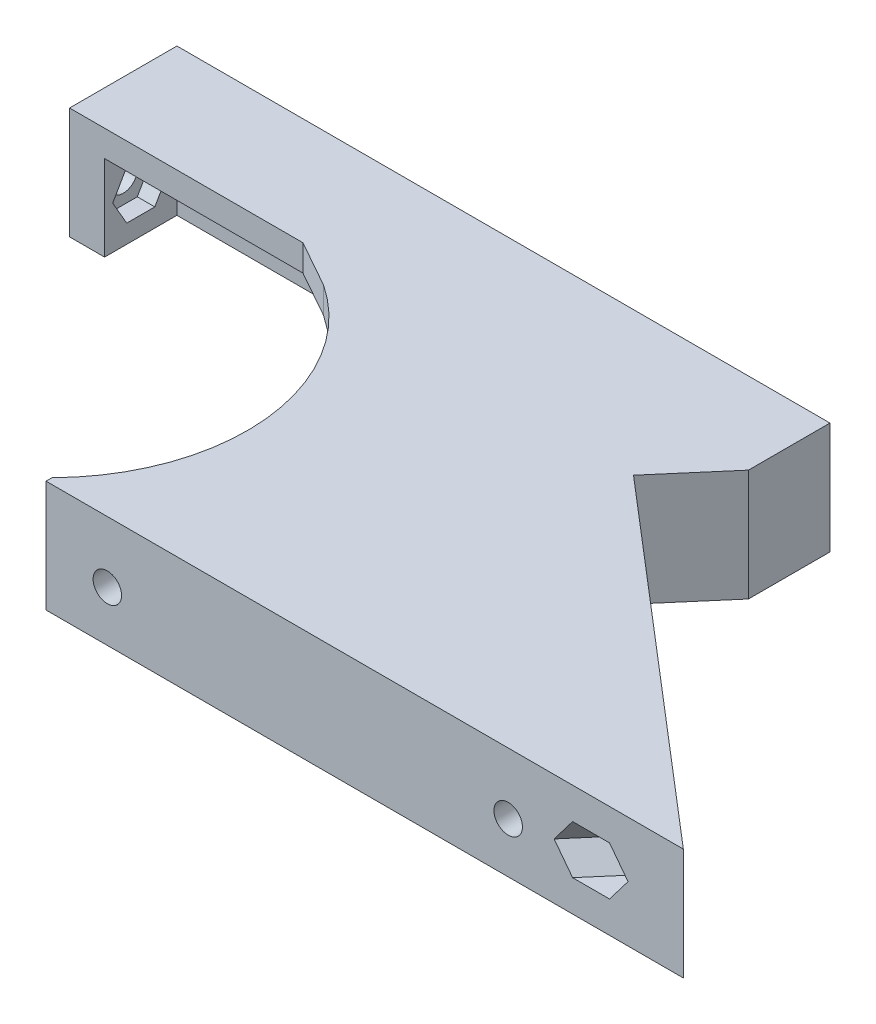
SolidWorks part; units mm, degrees
ref_plane "Alzado" through (0, 0, 0) normal (0, 0, 1) x (1, 0, 0)
ref_plane "Planta" through (0, 0, 0) normal (0, 1, 0) x (1, 0, 0)
ref_plane "Vista lateral" through (0, 0, 0) normal (1, 0, 0) x (0, 0, -1)
sketch "Croquis1" plane through (0, 0, 0) normal (0, 1, 0) x (1, 0, 0)
  line L0 (0, 0) -> (72.7832, 0)
  line L1 (72.7832, 0) -> (38.2245, 29.6204)
  line L2 (38.2245, 29.6204) -> (35.6214, 26.5833)
  line L3 (35.6214, 26.5833) -> (60.8031, 5)
  line L4 (60.8031, 5) -> (0, 5)
  line L5 (0, 5) -> (0, 0)
  dimension "D1" = 4
  dimension "D2" = 5
  dimension "D3" = 40.6
  dimension "D4" = 72.7832
extrude "Saliente-Extruir1" add sketch "Croquis1" along normal blind 12.75
sketch "Croquis2" plane through (0, 0, 0) normal (0, 0, 1) x (1, 0, 0)
  line L2 (0, 12.75) -> (72.7832, 12.75) construction
  line L3 (72.7832, 12.75) -> (72.7832, 0) construction
  circle A0 centre (52.7832, 5.75) radius 1.625
  circle A1 centre (7, 5.75) radius 1.625
  dimension "D1" = 3.25
  dimension "D2" = 20
  dimension "D3" = 7
  dimension "D4" = 45.7832
  dimension "D5" = 7
extrude "Cortar-Extruir1" cut sketch "Croquis2" against normal up to next
sketch "Croquis3" plane through (0, 12.75, 0) normal (0, 1, 0) x (1, 0, 0)
  line L0 (0, 5) -> (0, 0) construction
  line L1 (0, 0) -> (72.7832, 0) construction
  circle A0 centre (-16, 16.5) radius 22.5
  dimension "D1" = 45
  dimension "D2" = 16
  dimension "D3" = 16.5
extrude "Cortar-Extruir2" cut sketch "Croquis3" against normal through all
sketch "Croquis4" plane through (0, 12.75, 0) normal (0, 1, 0) x (1, 0, 0)
  line L0 (38.2245, 29.6204) -> (31.6563, 35.25)
  line L1 (31.6563, 35.25) -> (-3.5627, 35.25)
  line L2 (0, 0) -> (72.7832, 0) construction
  line L3 (72.7832, 0) -> (38.2245, 29.6204) construction
  line L4 (38.2245, 29.6204) -> (35.6214, 26.5833)
  line L5 (35.6214, 26.5833) -> (60.8031, 5)
  line L6 (60.8031, 5) -> (3.3391, 5)
  arc A0 (3.3391, 5) -> (-3.5627, 35.25) centre (-16, 16.5) ccw
  arc A1 (0, 0.6807) -> (3.3391, 5) centre (-16, 16.5) ccw construction
  dimension "D1" = 35.25
extrude "Saliente-Extruir2" add sketch "Croquis4" against normal blind 3
sketch "Croquis5" plane through (0, 9.75, 0) normal (0, -1, 0) x (1, 0, 0)
  line L0 (-3.5627, -35.25) -> (31.6563, -35.25)
  line L1 (31.6563, -35.25) -> (38.2245, -29.6204)
  line L2 (38.2245, -29.6204) -> (35.6214, -26.5833)
  line L3 (35.6214, -26.5833) -> (30.1767, -31.25)
  line L4 (30.1767, -31.25) -> (0.9908, -31.25)
  arc A0 (-3.5627, -35.25) -> (3.3391, -5) centre (-16, -16.5) ccw construction
  arc A1 (-3.5627, -35.25) -> (0.9908, -31.25) centre (-16, -16.5) ccw
  dimension "D1" = 4
extrude "Saliente-Extruir3" add sketch "Croquis5" along normal up to vertex (9.75 mm away) up to point (38.2245, 0, -29.6204)
sketch "Croquis6" plane through (30.8242, 0, -35.9632) normal (0.6508, 0, -0.7593) x (-0.7593, 0, -0.6508)
  line L0 (-55.2622, 12.75) -> (-55.2622, 0) construction
  circle A0 centre (-47.2622, 6.375) radius 1.625
  circle A1 centre (-7.4422, 6.375) radius 1.625
  dimension "D1" = 3.25
  dimension "D2" = 3.25
  dimension "D3" = 8
  dimension "D5" = 39.82
extrude "Cortar-Extruir3" cut sketch "Croquis6" against normal blind 10
sketch "Croquis7" plane through (28.2211, 0, -32.9261) normal (-0.6508, 0, 0.7593) x (0.7593, 0, 0.6508)
  line L1 (48.8643, 3.6) -> (50.4665, 6.375)
  line L2 (50.4665, 6.375) -> (48.8643, 9.15)
  line L3 (48.8643, 9.15) -> (45.66, 9.15)
  line L4 (45.66, 9.15) -> (44.0579, 6.375)
  line L5 (44.0579, 6.375) -> (45.66, 3.6)
  line L6 (45.66, 3.6) -> (48.8643, 3.6)
  circle A0 centre (47.2622, 6.375) radius 2.775 construction
  dimension "D1" = 5.55
extrude "Cortar-Extruir4" cut sketch "Croquis7" along normal blind 10 from offset 2 offset against normal yes
sketch "Croquis8" plane through (28.2211, 0, -32.9261) normal (-0.6508, 0, 0.7593) x (0.7593, 0, 0.6508)
  line L0 (45.66, 3.6) -> (48.8643, 3.6) construction
  line L1 (9.0443, 3.6) -> (10.6465, 6.375)
  line L2 (10.6465, 6.375) -> (9.0443, 9.15)
  line L3 (9.0443, 9.15) -> (5.84, 9.15)
  line L4 (5.84, 9.15) -> (4.2379, 6.375)
  line L5 (4.2379, 6.375) -> (5.84, 3.6)
  line L6 (5.84, 3.6) -> (9.0443, 3.6)
  circle A0 centre (7.4422, 6.375) radius 2.775 construction
extrude "Cortar-Extruir5" cut sketch "Croquis8" along normal blind 10 from offset 2 offset against normal yes
sketch "Croquis9" plane through (0, 0, -5) normal (0, 0, -1) x (-1, 0, 0)
  line L1 (-5.3979, 2.975) -> (-3.7957, 5.75)
  line L2 (-3.7957, 5.75) -> (-5.3979, 8.525)
  line L3 (-5.3979, 8.525) -> (-8.6021, 8.525)
  line L4 (-8.6021, 8.525) -> (-10.2043, 5.75)
  line L5 (-10.2043, 5.75) -> (-8.6021, 2.975)
  line L6 (-8.6021, 2.975) -> (-5.3979, 2.975)
  line L7 (-51.1811, 2.975) -> (-49.5789, 5.75)
  line L8 (-49.5789, 5.75) -> (-51.1811, 8.525)
  line L9 (-51.1811, 8.525) -> (-54.3853, 8.525)
  line L10 (-54.3853, 8.525) -> (-55.9875, 5.75)
  line L11 (-55.9875, 5.75) -> (-54.3853, 2.975)
  line L12 (-54.3853, 2.975) -> (-51.1811, 2.975)
  circle A0 centre (-7, 5.75) radius 2.775 construction
  circle A1 centre (-52.7832, 5.75) radius 2.775 construction
  dimension "D1" = 5.55
extrude "Cortar-Extruir6" cut sketch "Croquis9" against normal blind 2
sketch "Croquis10" plane through (0, 0, -35.25) normal (0, 0, -1) x (-1, 0, 0)
  line L0 (-31.6563, 0) -> (-31.6563, 12.75) construction
  circle A0 centre (-21.6563, 6.375) radius 1.625
  dimension "D1" = 3.25
  dimension "D2" = 10
extrude "Cortar-Extruir7" cut sketch "Croquis10" against normal up to next
sketch "Croquis11" plane through (0, 0, -31.25) normal (0, 0, 1) x (1, 0, 0)
  line L1 (23.2585, 3.6) -> (24.8606, 6.375)
  line L2 (24.8606, 6.375) -> (23.2585, 9.15)
  line L3 (23.2585, 9.15) -> (20.0542, 9.15)
  line L4 (20.0542, 9.15) -> (18.452, 6.375)
  line L5 (18.452, 6.375) -> (20.0542, 3.6)
  line L6 (20.0542, 3.6) -> (23.2585, 3.6)
  circle A0 centre (21.6563, 6.375) radius 2.775 construction
  dimension "D1" = 5.55
extrude "Cortar-Extruir8" cut sketch "Croquis11" against normal blind 2
mirror "Simetría1" about plane through (0, 0, 0) normal (0, 1, 0) of bodies 111
sketch "Croquis12" plane through (0, 0, -35.25) normal (0, 0, -1) x (-1, 0, 0)
  line L1 (-79.3319, 0) -> (13.1768, 0)
  line L2 (-79.3319, 0) -> (-79.3319, 24.2558)
  line L3 (-79.3319, 24.2558) -> (13.1768, 24.2558)
  line L4 (13.1768, 0) -> (13.1768, 24.2558)
extrude "Cortar-Extruir9" cut sketch "Croquis12" against normal through all both and the other way through all
sketch "Croquis13" plane through (0, -12.75, 0) normal (0, -1, 0) x (1, 0, 0)
  line L1 (-35.5627, -82.3826) -> (-35.5627, -38.25)
  line L3 (-3.5627, -35.25) -> (31.6563, -35.25)
  line L5 (31.6563, -35.25) -> (0.0002, -62.3826)
  line L6 (0.0002, -62.3826) -> (-35.5627, -82.3826)
  line L7 (72.7832, 0) -> (31.6563, -35.25) construction
  line L8 (-3.5627, -35.25) -> (-8.9133, -38.25)
  line L9 (-8.9133, -38.25) -> (-35.5627, -38.25)
  dimension "D1" = 32
  dimension "D2" = 3
  dimension "D3" = 20
extrude "Saliente-Extruir4" add sketch "Croquis13" against normal up to vertex (12.75 mm away) up to point (31.6563, 0, -35.25)
sketch "Croquis14" plane through (0, 0, 0) normal (0, 1, 0) x (1, 0, 0)
  line L3 (30.1767, 31.25) -> (0.9908, 31.25)
  line L4 (0.9908, 31.25) -> (-31.5627, 38.25)
  line L6 (-31.5627, 38.25) -> (-31.5627, 75.5439)
  line L7 (-2.3039, 59.0892) -> (70.1801, -3.0371)
  line L8 (-31.5627, 75.5439) -> (-2.3039, 59.0892)
  line L9 (-31.5627, 38.25) -> (-31.5627, 75.5439)
  line L10 (-2.3039, 59.0892) -> (30.1767, 31.25)
  line L11 (-31.5627, 75.5439) -> (-2.3039, 59.0892)
  dimension "D1" = 4
extrude "Cortar-Extruir10" cut sketch "Croquis14" against normal up to vertex (9.75 mm away) up to point (0.9908, -9.75, -31.25)
sketch "Croquis16" plane through (30.8242, 0, -35.9632) normal (0.6508, 0, -0.7593) x (-0.7593, 0, -0.6508)
  line L0 (40.5969, 0) -> (-55.2622, 0) construction
  line L1 (-27.4422, 0) -> (40.5969, 0)
  line L2 (-27.4422, 0) -> (-27.4422, -12.75)
  line L3 (-27.4422, -12.75) -> (40.5969, -12.75)
  line L4 (40.5969, 0) -> (40.5969, -12.75)
  circle A0 centre (-7.4422, -6.375) radius 1.625 construction
  dimension "D1" = 20
  dimension "D2" = 68.0391
extrude "Cortar-Extruir11" cut sketch "Croquis16" against normal blind 1
sketch "Croquis17" plane through (0, -12.75, 0) normal (0, -1, 0) x (1, 0, 0)
  line L1 (0.0002, -61.6233) -> (-40.6573, -61.6233)
  line L2 (0.0002, -61.6233) -> (0.0002, -84.5579)
  line L3 (0.0002, -84.5579) -> (-40.6573, -84.5579)
  line L4 (-40.6573, -61.6233) -> (-40.6573, -84.5579)
extrude "Cortar-Extruir12" cut sketch "Croquis17" against normal through all both and the other way through all
sketch "Croquis18" plane through (0, 0, 0) normal (0, 1, 0) x (1, 0, 0)
  line L0 (60.8031, 5) -> (-2.3039, 59.0892) construction
  line L1 (-35.5627, 61.6233) -> (-0.6506, 61.6233)
  line L2 (-35.5627, 61.6233) -> (-35.5627, 57.6722)
  line L3 (-35.5627, 57.6722) -> (-0.6506, 57.6722)
  line L4 (-0.6506, 61.6233) -> (-0.6506, 57.6722)
extrude "Saliente-Extruir5" add sketch "Croquis18" against normal up to surface (9.75 mm away) up to face at (-1.8156, -9.75, -38.1832)
sketch "Croquis20" plane through (30.1734, 0, -35.2039) normal (0.6508, 0, -0.7593) x (-0.7593, 0, -0.6508)
  line L2 (40.5969, -12.75) -> (40.5969, 0) construction
  circle A0 centre (25.5969, -6.375) radius 1.625
  circle A1 centre (-7.4422, -6.375) radius 1.625 construction
  circle A2 centre (-7.4422, -6.375) radius 1.625
  dimension "D2" = 33.0391
  dimension "D1" = 15
extrude "Cortar-Extruir14" cut sketch "Croquis20" against normal blind 10
sketch "Croquis21" plane through (28.2211, 0, -32.9261) normal (-0.6508, 0, 0.7593) x (0.7593, 0, 0.6508)
  line L0 (9.0443, -9.15) -> (5.84, -9.15) construction
  line L1 (-23.9947, -9.15) -> (-22.3926, -6.375)
  line L2 (-22.3926, -6.375) -> (-23.9947, -3.6)
  line L3 (-23.9947, -3.6) -> (-27.199, -3.6)
  line L4 (-27.199, -3.6) -> (-28.8012, -6.375)
  line L5 (-28.8012, -6.375) -> (-27.199, -9.15)
  line L6 (-27.199, -9.15) -> (-23.9947, -9.15)
  circle A0 centre (-25.5969, -6.375) radius 2.775 construction
extrude "Cortar-Extruir15" cut sketch "Croquis21" against normal up to vertex (2 mm away) up to point (36.3898, -9.15, -28.5588)
sketch "Croquis22" plane through (0, 0, -61.6233) normal (0, 0, -1) x (-1, 0, 0)
  line L0 (35.5627, -12.75) -> (35.5627, 0) construction
  circle A0 centre (18.1127, -6.375) radius 1.625
  dimension "D1" = 3.25
  dimension "D2" = 17.45
extrude "Cortar-Extruir16" cut sketch "Croquis22" against normal blind 10
sketch "Croquis23" plane through (0, 0, -57.6722) normal (0, 0, 1) x (1, 0, 0)
  line L0 (7.5697, -9.15) -> (10.0026, -9.15) construction
  line L1 (-16.5105, -9.15) -> (-14.9084, -6.375)
  line L2 (-14.9084, -6.375) -> (-16.5105, -3.6)
  line L3 (-16.5105, -3.6) -> (-19.7148, -3.6)
  line L4 (-19.7148, -3.6) -> (-21.317, -6.375)
  line L5 (-21.317, -6.375) -> (-19.7148, -9.15)
  line L6 (-19.7148, -9.15) -> (-16.5105, -9.15)
  circle A0 centre (-18.1127, -6.375) radius 2.775 construction
extrude "Cortar-Extruir17" cut sketch "Croquis23" against normal blind 2
sketch "Croquis26" plane through (0, 0, 0) normal (0, 1, 0) x (1, 0, 0)
  line L0 (60.8031, 5) -> (-2.2878, 59.0754)
  line L1 (60.8031, 5) -> (60.1523, 4.2407)
  line L2 (-2.2878, 59.0754) -> (-2.9386, 58.3161)
  line L3 (60.1523, 4.2407) -> (-2.9386, 58.3161)
  line L5 (60.8031, 5) -> (-0.6506, 57.6722) construction
  dimension "D1" = 1
extrude "Saliente-Extruir6" add sketch "Croquis26" against normal up to vertex (12.75 mm away) up to point (-0.6506, -12.75, -61.6233)
sketch "Croquis27" plane through (27.5703, 0, -32.1669) normal (-0.6508, 0, 0.7593) x (0.7593, 0, 0.6508)
  line L0 (9.0443, -9.15) -> (5.84, -9.15) construction
  line L1 (-22.4214, -6.375) -> (-24.0092, -3.625)
  line L2 (-24.0092, -3.625) -> (-27.1846, -3.625)
  line L3 (-27.1846, -3.625) -> (-28.7723, -6.375)
  line L4 (-28.7723, -6.375) -> (-27.1846, -9.125)
  line L5 (-27.1846, -9.125) -> (-24.0092, -9.125)
  line L6 (-24.0092, -9.125) -> (-22.4214, -6.375)
  line L7 (10.6465, -6.375) -> (9.0443, -3.6)
  line L8 (9.0443, -3.6) -> (5.84, -3.6)
  line L9 (5.84, -3.6) -> (4.2379, -6.375)
  line L10 (4.2379, -6.375) -> (5.84, -9.15)
  line L11 (5.84, -9.15) -> (9.0443, -9.15)
  line L12 (9.0443, -9.15) -> (10.6465, -6.375)
  circle A0 centre (-25.5969, -6.375) radius 2.75 construction
  circle A1 centre (7.4422, -6.375) radius 2.775 construction
extrude "Cortar-Extruir18" cut sketch "Croquis27" against normal blind 2
sketch "Croquis28" plane through (29.5227, 0, -34.4447) normal (-0.6508, 0, 0.7593) x (0.7593, 0, 0.6508)
  line L1 (-24.0092, -3.625) -> (-27.1846, -3.625)
  line L2 (-27.1846, -3.625) -> (-28.7723, -6.375)
  line L3 (-28.7723, -6.375) -> (-27.1846, -9.125)
  line L4 (-27.1846, -9.125) -> (-24.0092, -9.125)
  line L5 (-24.0092, -9.125) -> (-22.4214, -6.375)
  line L6 (-22.4214, -6.375) -> (-24.0092, -3.625)
  line L7 (10.6465, -6.375) -> (9.0443, -3.6)
  line L8 (9.0443, -3.6) -> (5.84, -3.6)
  line L9 (5.84, -3.6) -> (4.2379, -6.375)
  line L10 (4.2379, -6.375) -> (5.84, -9.15)
  line L11 (5.84, -9.15) -> (9.0443, -9.15)
  line L12 (9.0443, -9.15) -> (10.6465, -6.375)
  circle A0 centre (-25.5969, -6.375) radius 2.75 construction
  circle A1 centre (7.4422, -6.375) radius 2.775 construction
  circle A2 centre (-25.5969, -6.375) radius 1.625
  circle A3 centre (7.4422, -6.375) radius 1.625
extrude "Saliente-Extruir7" add sketch "Croquis28" along normal blind 1
sketch "Croquis29" plane through (-35.5627, 0, 0) normal (-1, 0, 0) x (0, 0, 1)
  line L0 (-61.6233, -12.75) -> (-61.6233, 0) construction
  line L1 (-38.25, 0) -> (-61.6233, 0) construction
  circle A0 centre (-51.6233, -6.375) radius 1.625
  dimension "D3" = 3.25
  dimension "D1" = 10
  dimension "D2" = 6.375
extrude "Cortar-Extruir19" cut sketch "Croquis29" against normal up to next
sketch "Croquis30" plane through (-31.5627, 0, 0) normal (1, 0, 0) x (0, 0, -1)
  line L8 (53.2255, -9.15) -> (54.8276, -6.375)
  line L9 (54.8276, -6.375) -> (53.2255, -3.6)
  line L10 (53.2255, -3.6) -> (50.0212, -3.6)
  line L11 (50.0212, -3.6) -> (48.419, -6.375)
  line L12 (48.419, -6.375) -> (50.0212, -9.15)
  line L13 (50.0212, -9.15) -> (53.2255, -9.15)
  circle A0 centre (51.6233, -6.375) radius 2.775 construction
  dimension "D1" = 5.55
extrude "Cortar-Extruir20" cut sketch "Croquis30" against normal blind 2
sketch "Croquis40" plane through (0, -12.75, 0) normal (0, -1, 0) x (1, 0, 0)
  line L0 (51.0095, -17.3453) -> (-0.6506, -61.6233)
  line L1 (51.0095, -17.3453) -> (51.6603, -18.1045)
  line L2 (51.6603, -18.1045) -> (0.886, -61.6233)
  line L3 (0.886, -61.6233) -> (-0.6506, -61.6233)
extrude "Saliente-Extruir11" add sketch "Croquis40" against normal up to surface (12.75 mm away) up to face at (7.777, 0, -27.7785)
sketch "Croquis41" plane through (30.8242, 0, -35.9632) normal (0.6508, 0, -0.7593) x (-0.7593, 0, -0.6508)
  circle A0 centre (-7.4422, -6.375) radius 1.625
  circle A1 centre (25.5969, -6.375) radius 1.625
extrude "Cortar-Extruir25" cut sketch "Croquis41" against normal blind 10
sketch "Croquis42" plane through (0, -12.75, 0) normal (0, -1, 0) x (1, 0, 0)
  line L1 (72.7832, 0) -> (0.886, -61.6233) construction
  line L2 (32.9594, -34.1331) -> (39.0181, -41.2019)
  line L3 (39.0181, -41.2019) -> (24.7121, -41.2019)
  line L4 (32.9594, -34.1331) -> (24.7121, -41.2019)
  dimension "D2" = 9.31
extrude "Saliente-Extruir12" add sketch "Croquis42" against normal up to surface (12.75 mm away) up to face at (-0.0029, 0, -29.6064)
sketch "Croquis43" plane through (0, -12.75, 0) normal (0, -1, 0) x (1, 0, 0)
  line L0 (39.0181, -41.2019) -> (39.0181, -50.5119)
  line L1 (39.0181, -50.5119) -> (13.8499, -50.5119)
  line L2 (-35.5627, -38.25) -> (-35.5627, -61.6233) construction
  line L3 (39.0181, -41.2019) -> (24.7121, -41.2019)
  line L4 (24.7121, -41.2019) -> (13.8499, -50.5119)
  dimension "D1" = 9.31
extrude "Saliente-Extruir13" add sketch "Croquis43" against normal up to surface (12.75 mm away) up to face at (6.9041, 0, -31.5862)
sketch "Croquis44" plane through (0, -12.75, 0) normal (0, -1, 0) x (1, 0, 0)
  line L0 (13.8499, -50.5119) -> (-35.5627, -50.5119)
  line L1 (-35.5627, -38.25) -> (-35.5627, -61.6233) construction
  line L2 (-35.5627, -50.5119) -> (-35.5627, -61.6233)
  line L3 (-35.5627, -61.6233) -> (0.886, -61.6233)
  line L4 (0.886, -61.6233) -> (13.8499, -50.5119)
extrude "Cortar-Extruir26" cut sketch "Croquis44" against normal through all
sketch "Croquis45" plane through (0, 0, 0) normal (0, 1, 0) x (1, 0, 0)
  line L0 (6.1668, 50.5119) -> (21.7241, 50.5119)
  line L1 (39.0181, 50.5119) -> (6.1668, 50.5119) construction
  line L2 (21.7241, 50.5119) -> (21.7241, 37.1777)
  line L3 (6.1668, 50.5119) -> (59.2664, 5) construction
  line L4 (21.7241, 37.1777) -> (6.1668, 50.5119)
extrude "Saliente-Extruir14" add sketch "Croquis45" against normal up to surface (9.75 mm away) up to face at (-0.1116, -9.75, -32.022)
sketch "Croquis46" plane through (0, 0, 0) normal (0, 1, 0) x (1, 0, 0)
  line L0 (6.1668, 50.5119) -> (59.2664, 5) construction
  line L1 (-35.5627, 50.5119) -> (-31.5627, 50.5119)
  line L2 (-35.5627, 50.5119) -> (-35.5627, 38.25)
  line L3 (-35.5627, 38.25) -> (-31.5627, 38.25)
  line L4 (-31.5627, 46.5119) -> (-31.5627, 38.25)
  line L5 (-31.5627, 50.5119) -> (10.8337, 50.5119)
  line L7 (-31.5627, 46.5119) -> (10.8337, 46.5119)
  line L8 (10.8337, 50.5119) -> (10.8337, 46.5119)
  dimension "D1" = 4
extrude "Saliente-Extruir15" add sketch "Croquis46" against normal up to surface (9.75 mm away) up to face at (-0.1116, -9.75, -32.022)
sketch "Croquis47" plane through (-35.5627, 0, 0) normal (-1, 0, 0) x (0, 0, 1)
  circle A0 centre (-42.381, -4.875) radius 1.625
  dimension "D1" = 3.25
extrude "Cortar-Extruir27" cut sketch "Croquis47" against normal up to next
sketch "Croquis48" plane through (-35.5627, 0, 0) normal (-1, 0, 0) x (0, 0, 1)
  line L1 (-40.7788, -7.65) -> (-39.1767, -4.875)
  line L2 (-39.1767, -4.875) -> (-40.7788, -2.1)
  line L3 (-40.7788, -2.1) -> (-43.9831, -2.1)
  line L4 (-43.9831, -2.1) -> (-45.5853, -4.875)
  line L5 (-45.5853, -4.875) -> (-43.9831, -7.65)
  line L6 (-43.9831, -7.65) -> (-40.7788, -7.65)
  circle A0 centre (-42.381, -4.875) radius 2.775 construction
  dimension "D1" = 5.55
extrude "Cortar-Extruir28" cut sketch "Croquis48" against normal up to next from offset 2 offset against normal yes
sketch "Croquis49" plane through (0, 0, 0) normal (0, 1, 0) x (1, 0, 0)
  line L0 (26.6685, 32.9398) -> (35.0181, 42.6816)
  line L1 (10.8337, 46.5119) -> (59.2664, 5) construction
  line L2 (35.0181, 42.6816) -> (35.0181, 46.5119)
  line L3 (35.0181, 46.5119) -> (10.8337, 46.5119)
  line L4 (10.8337, 46.5119) -> (26.6685, 32.9398)
  line L5 (39.0181, 41.2019) -> (39.0181, 50.5119) construction
  line L6 (32.9594, 34.1331) -> (39.0181, 41.2019) construction
  dimension "D1" = 4
  dimension "D2" = 4
extrude "Cortar-Extruir29" cut sketch "Croquis49" against normal up to surface (9.75 mm away) up to face at (0.5551, -9.75, -30.8791)
sketch "Croquis50" plane through (0, 0, -50.5119) normal (0, 0, -1) x (-1, 0, 0)
  line L0 (35.5627, 0) -> (35.5627, -12.75) construction
  line L1 (31.5627, -9.75) -> (-35.0181, -9.75) construction
  circle A0 centre (25.5627, -6.75) radius 1.625
  circle A1 centre (-24.4373, -6.75) radius 1.625
  dimension "D1" = 3.25
  dimension "D2" = 3.25
  dimension "D4" = 50
  dimension "D5" = 3
  dimension "D3" = 10
extrude "Cortar-Extruir30" cut sketch "Croquis50" against normal up to next
sketch "Croquis51" plane through (0, 0, -50.5119) normal (0, 0, -1) x (-1, 0, 0)
  line L1 (-22.8352, -9.525) -> (-21.233, -6.75)
  line L2 (-21.233, -6.75) -> (-22.8352, -3.975)
  line L3 (-22.8352, -3.975) -> (-26.0395, -3.975)
  line L4 (-26.0395, -3.975) -> (-27.6416, -6.75)
  line L5 (-27.6416, -6.75) -> (-26.0395, -9.525)
  line L6 (-26.0395, -9.525) -> (-22.8352, -9.525)
  line L7 (27.1648, -9.525) -> (28.767, -6.75)
  line L8 (28.767, -6.75) -> (27.1648, -3.975)
  line L9 (27.1648, -3.975) -> (23.9605, -3.975)
  line L10 (23.9605, -3.975) -> (22.3584, -6.75)
  line L11 (22.3584, -6.75) -> (23.9605, -9.525)
  line L12 (23.9605, -9.525) -> (27.1648, -9.525)
  circle A0 centre (-24.4373, -6.75) radius 2.775 construction
  circle A1 centre (25.5627, -6.75) radius 2.775 construction
  dimension "D1" = 5.55
extrude "Cortar-Extruir31" cut sketch "Croquis51" against normal up to next from offset 2 offset against normal yes
mirror "Simetría2" about plane through (0, -12.75, 0) normal (0, -1, 0) of bodies 148 118
sketch "Croquis19" plane through (0, 0, -61.6233) normal (0, 0, -1) x (-1, 0, 0)
  line L1 (-78.7832, -12.75) -> (41.6655, -12.75)
  line L2 (-78.7832, -12.75) -> (-78.7832, 20.1367)
  line L3 (-78.7832, 20.1367) -> (41.6655, 20.1367)
  line L4 (41.6655, -12.75) -> (41.6655, 20.1367)
extrude "Cortar-Extruir13" cut sketch "Croquis19" against normal through all both and the other way through all
